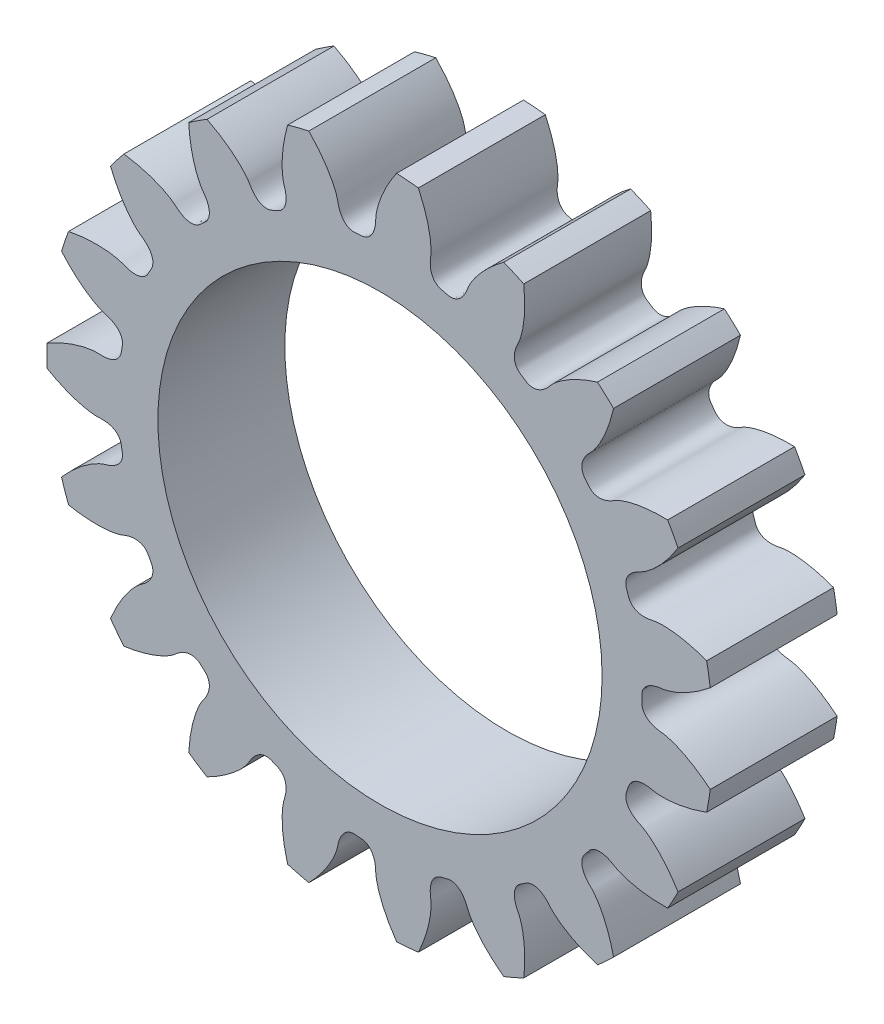
SolidWorks part; units mm, degrees
ref_plane "Front Plane" through (0, 0, 0) normal (0, 0, 1) x (1, 0, 0)
ref_plane "Top Plane" through (0, 0, 0) normal (0, 1, 0) x (1, 0, 0)
ref_plane "Right Plane" through (0, 0, 0) normal (1, 0, 0) x (0, 0, -1)
ref_axis "Axis1" through (0, 0, 55) along (0, 0, -1)
sketch "SketchRevolveSpurPinion" plane through (0, 0, 0) normal (1, 0, 0) x (0, 0, -1)
  line L0 (0, 0) -> (1, 0) construction
  line L1 (-2, 0) -> (-2, 10.5)
  line L2 (-2, 10.5) -> (2, 10.5)
  line L3 (2, 10.5) -> (2, 0)
  line L4 (2, 0) -> (-2, 0)
  dimension "Side1" = 2
  dimension "OutsideRadius" = 10.5
  dimension "Side2" = 2
revolve "SpurPinion" add sketch "SketchRevolveSpurPinion" angle 360 about L0
sketch "SketchToothSpurPinion" plane through (0, 0, 0) normal (0, 0, 1) x (1, 0, 0)
  arc A0 (10.4533, 1.4254) -> (10.4533, -1.4254) centre (0, 0) cw
  spline S0 degree 3 poles (10.4533, -1.4254) (10.3673, -1.3534) (10.2387, -1.2519) (10.0656, -1.1286) (9.9441, -1.0476) (9.8276, -0.9751) (9.7165, -0.9108) (9.6112, -0.8542) (9.5121, -0.8048) (9.4196, -0.7623) (9.334, -0.7262) (9.2555, -0.696) (9.1845, -0.6711) (9.1211, -0.6512) (9.0657, -0.6356) (9.0184, -0.624) (8.9795, -0.6156) (8.949, -0.61) (8.8788, -0.5998) (8.8005, -0.5931) (8.7144, -0.5742) (8.6645, -0.561) (8.6165, -0.5455) (8.5703, -0.5277) (8.5256, -0.5072) (8.4824, -0.4836) (8.4406, -0.4563) (8.4001, -0.4244) (8.3612, -0.3869) (8.3249, -0.3424) (8.2927, -0.2898) (8.2672, -0.2288) (8.2531, -0.1657) (8.2473, -0.0886) (8.2517, 0) (8.2473, 0.0886) (8.2531, 0.1657) (8.2672, 0.2288) (8.2927, 0.2898) (8.3249, 0.3424) (8.3612, 0.3869) (8.4001, 0.4244) (8.4406, 0.4563) (8.4824, 0.4836) (8.5256, 0.5072) (8.5703, 0.5277) (8.6165, 0.5455) (8.6645, 0.561) (8.7144, 0.5742) (8.8005, 0.5931) (8.8788, 0.5998) (8.949, 0.61) (8.9795, 0.6156) (9.0184, 0.624) (9.0657, 0.6356) (9.1211, 0.6512) (9.1845, 0.6711) (9.2555, 0.696) (9.334, 0.7262) (9.4196, 0.7623) (9.5121, 0.8048) (9.6112, 0.8542) (9.7165, 0.9108) (9.8276, 0.9751) (9.9441, 1.0476) (10.0656, 1.1286) (10.2387, 1.2519) (10.3673, 1.3534) (10.4533, 1.4254) knots 0 0 0 0 0.060396 0.08821 0.114435 0.13907 0.162116 0.183572 0.203439 0.221717 0.238406 0.253505 0.267014 0.278934 0.289265 0.298007 0.305159 0.310722 0.314695 0.343385 0.352907 0.362159 0.371189 0.380056 0.388837 0.397627 0.406544 0.415731 0.425355 0.435593 0.446599 0.458448 0.471063 0.481231 0.5 0.518769 0.528937 0.541552 0.553401 0.564407 0.574645 0.584269 0.593456 0.602373 0.611163 0.619944 0.628811 0.637841 0.647093 0.656615 0.685305 0.689278 0.694841 0.701993 0.710735 0.721066 0.732986 0.746495 0.761594 0.778283 0.796561 0.816428 0.837884 0.86093 0.885565 0.91179 0.939604 1 1 1 1
extrude "ToothExtrudeCutSpurPinion" cut sketch "SketchToothSpurPinion" against normal blind 2 and the other way blind 2
pattern_circular "PatternSpurPinion" count 19 every 18.947 about axis through (0, 0, 55) along (0, 0, -1) of "ToothExtrudeCutSpurPinion"
sketch "BoreRevolveSketch" plane through (0, 0, 0) normal (1, 0, 0) x (0, 0, -1)
  line L0 (0, 0) -> (1, 0) construction
  line L1 (-2, 0) -> (2, 0)
  line L2 (2, 0) -> (2, 7)
  line L3 (2, 7) -> (-2, 7)
  line L4 (-2, 7) -> (-2, 0)
  dimension "BoreSide1" = 2
  dimension "TaperSide1" = 7
  dimension "BoreSide2" = 2
  dimension "TaperSide2" = 7
revolve "BoreRevolveCut" cut sketch "BoreRevolveSketch" angle 360 about L0
sketch "AuxiliarySketchSpurPinion" plane through (0, 0, 0) normal (0, 0, 1) x (1, 0, 0)
  circle A0 centre (0, 0) radius 9.5 construction
  circle A1 centre (0, 0) radius 8.9271 construction
  circle A2 centre (0, 0) radius 8.9287 construction
  circle A3 centre (0, 0) radius 10.5 construction
  circle A4 centre (0, 0) radius 8.25 construction
  dimension "PitchDiameter" = 19
  dimension "BaseDiameter" = 17.8542
  dimension "FormDiameter" = 17.8575
  dimension "MajorDiameter" = 21
  dimension "MinorDiameter" = 16.5
